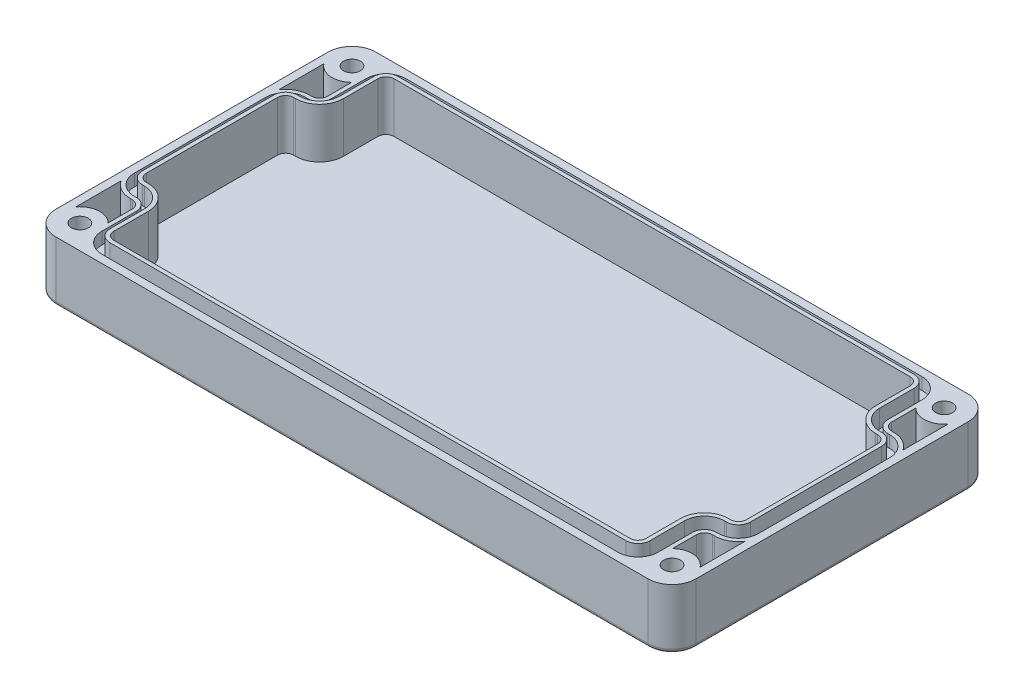
SolidWorks part; units mm, degrees
ref_plane "Спереди" through (0, 0, 0) normal (0, 0, 1) x (1, 0, 0)
ref_plane "Сверху" through (0, 0, 0) normal (0, 1, 0) x (1, 0, 0)
ref_plane "Справа" through (0, 0, 0) normal (1, 0, 0) x (0, 0, -1)
sketch "Эскиз1" plane through (0, 0, 0) normal (0, 1, 0) x (1, 0, 0)
  line L1 (-74, 40) -> (74, 40)
  line L2 (-80, 34) -> (-80, -34)
  line L3 (-74, -40) -> (74, -40)
  line L4 (80, 34) -> (80, -34)
  line L5 (-80, 40) -> (80, -40) construction
  line L6 (-80, -40) -> (80, 40) construction
  arc A0 (74, 40) -> (80, 34) centre (74, 34) cw
  arc A1 (80, -34) -> (74, -40) centre (74, -34) cw
  arc A2 (-74, -40) -> (-80, -34) centre (-74, -34) cw
  arc A3 (-80, 34) -> (-74, 40) centre (-74, 34) cw
  point P0 (0, 0)
  dimension "D3" = 6
  dimension "D1" = 160
  dimension "D2" = 80
extrude "Бобышка-Вытянуть1" add sketch "Эскиз1" along normal blind 15
sketch "Эскиз2" plane through (0, 0, 0) normal (0, 1, 0) x (1, 0, 0)
  line L0 (-66.5, 33) -> (-66.5, 24.4)
  line L1 (-72.5, 18.4) -> (-73, 18.4)
  line L2 (-75, 16.4) -> (-75, -16.4)
  line L3 (-73, -18.4) -> (-72.5, -18.4)
  line L4 (-66.5, -24.4) -> (-66.5, -33)
  line L5 (-64.5, -35) -> (64.5, -35)
  line L6 (66.5, -33) -> (66.5, -24.4)
  line L7 (72.5, -18.4) -> (73, -18.4)
  line L8 (75, -16.4) -> (75, 16.4)
  line L9 (73, 18.4) -> (72.5, 18.4)
  line L10 (66.5, 24.4) -> (66.5, 33)
  line L11 (64.5, 35) -> (-64.5, 35)
  line L12 (-75, 0) -> (75, 0) construction
  line L13 (0, 35) -> (0, -35) construction
  arc A0 (66.5, 24.4) -> (72.5, 18.4) centre (72.5, 24.4) ccw
  arc A1 (72.5, -18.4) -> (66.5, -24.4) centre (72.5, -24.4) ccw
  arc A2 (-66.5, -24.4) -> (-72.5, -18.4) centre (-72.5, -24.4) ccw
  arc A3 (-72.5, 18.4) -> (-66.5, 24.4) centre (-72.5, 24.4) ccw
  arc A4 (64.5, 35) -> (66.5, 33) centre (64.5, 33) cw
  arc A5 (73, 18.4) -> (75, 16.4) centre (73, 16.4) cw
  arc A6 (75, -16.4) -> (73, -18.4) centre (73, -16.4) cw
  arc A7 (66.5, -33) -> (64.5, -35) centre (64.5, -33) cw
  arc A8 (-64.5, -35) -> (-66.5, -33) centre (-64.5, -33) cw
  arc A9 (-73, -18.4) -> (-75, -16.4) centre (-73, -16.4) cw
  arc A10 (-75, 16.4) -> (-73, 18.4) centre (-73, 16.4) cw
  arc A11 (-66.5, 33) -> (-64.5, 35) centre (-64.5, 33) cw
  dimension "D4" = 150
  dimension "D1" = 6
  dimension "D2" = 2
  dimension "D3" = 70
  dimension "D5" = 36.8
  dimension "D6" = 133
extrude "Вырез-Вытянуть1" cut sketch "Эскиз2" along normal up to surface (15 mm away) from offset 4 up to face at (0, 15, 0)
sketch "Эскиз3" plane through (0, 0, 0) normal (0, 1, 0) x (1, 0, 0)
  line L8 (-78, 34) -> (-78, -34)
  line L9 (-74, -38) -> (74, -38)
  line L10 (78, -34) -> (78, 34)
  line L11 (74, 38) -> (-74, 38)
  line L12 (-78, 34) -> (-78, -34)
  line L13 (-74, -38) -> (74, -38)
  line L14 (78, -34) -> (78, 34)
  line L15 (74, 38) -> (-74, 38)
  line L36 (70.5, 24.4) -> (70.5, 33)
  line L37 (73, 22.4) -> (72.5, 22.4)
  line L38 (79, -16.4) -> (79, 16.4)
  line L39 (72.5, -22.4) -> (73, -22.4)
  line L40 (70.5, -33) -> (70.5, -24.4)
  line L41 (-64.5, -39) -> (64.5, -39)
  line L42 (-70.5, -24.4) -> (-70.5, -33)
  line L43 (-73, -22.4) -> (-72.5, -22.4)
  line L44 (-79, 16.4) -> (-79, -16.4)
  line L45 (-72.5, 22.4) -> (-73, 22.4)
  line L46 (-70.5, 33) -> (-70.5, 24.4)
  line L47 (64.5, 39) -> (-64.5, 39)
  line L48 (70.5, 24.4) -> (70.5, 33)
  line L49 (73, 22.4) -> (72.5, 22.4)
  line L50 (79, -16.4) -> (79, 16.4)
  line L51 (72.5, -22.4) -> (73, -22.4)
  line L52 (70.5, -33) -> (70.5, -24.4)
  line L53 (-64.5, -39) -> (64.5, -39)
  line L54 (-70.5, -24.4) -> (-70.5, -33)
  line L55 (-73, -22.4) -> (-72.5, -22.4)
  line L56 (-79, 16.4) -> (-79, -16.4)
  line L57 (-72.5, 22.4) -> (-73, 22.4)
  line L58 (-70.5, 33) -> (-70.5, 24.4)
  line L59 (64.5, 39) -> (-64.5, 39)
  circle A0 centre (-74, 34) radius 5
  arc A8 (-74, 38) -> (-78, 34) centre (-74, 34) ccw
  arc A9 (-78, -34) -> (-74, -38) centre (-74, -34) ccw
  arc A10 (74, -38) -> (78, -34) centre (74, -34) ccw
  arc A11 (78, 34) -> (74, 38) centre (74, 34) ccw
  arc A12 (-74, 38) -> (-78, 34) centre (-74, 34) ccw
  arc A13 (-78, -34) -> (-74, -38) centre (-74, -34) ccw
  arc A14 (74, -38) -> (78, -34) centre (74, -34) ccw
  arc A15 (78, 34) -> (74, 38) centre (74, 34) ccw
  arc A36 (70.5, 33) -> (64.5, 39) centre (64.5, 33) ccw
  arc A37 (70.5, 24.4) -> (72.5, 22.4) centre (72.5, 24.4) ccw
  arc A38 (79, 16.4) -> (73, 22.4) centre (73, 16.4) ccw
  arc A39 (73, -22.4) -> (79, -16.4) centre (73, -16.4) ccw
  arc A40 (72.5, -22.4) -> (70.5, -24.4) centre (72.5, -24.4) ccw
  arc A41 (64.5, -39) -> (70.5, -33) centre (64.5, -33) ccw
  arc A42 (-70.5, -33) -> (-64.5, -39) centre (-64.5, -33) ccw
  arc A43 (-70.5, -24.4) -> (-72.5, -22.4) centre (-72.5, -24.4) ccw
  arc A44 (-79, -16.4) -> (-73, -22.4) centre (-73, -16.4) ccw
  arc A45 (-73, 22.4) -> (-79, 16.4) centre (-73, 16.4) ccw
  arc A46 (-72.5, 22.4) -> (-70.5, 24.4) centre (-72.5, 24.4) ccw
  arc A47 (-64.5, 39) -> (-70.5, 33) centre (-64.5, 33) ccw
  arc A48 (70.5, 33) -> (64.5, 39) centre (64.5, 33) ccw
  arc A49 (70.5, 24.4) -> (72.5, 22.4) centre (72.5, 24.4) ccw
  arc A50 (79, 16.4) -> (73, 22.4) centre (73, 16.4) ccw
  arc A51 (73, -22.4) -> (79, -16.4) centre (73, -16.4) ccw
  arc A52 (72.5, -22.4) -> (70.5, -24.4) centre (72.5, -24.4) ccw
  arc A53 (64.5, -39) -> (70.5, -33) centre (64.5, -33) ccw
  arc A54 (-70.5, -33) -> (-64.5, -39) centre (-64.5, -33) ccw
  arc A55 (-70.5, -24.4) -> (-72.5, -22.4) centre (-72.5, -24.4) ccw
  arc A56 (-79, -16.4) -> (-73, -22.4) centre (-73, -16.4) ccw
  arc A57 (-73, 22.4) -> (-79, 16.4) centre (-73, 16.4) ccw
  arc A58 (-72.5, 22.4) -> (-70.5, 24.4) centre (-72.5, 24.4) ccw
  arc A59 (-64.5, 39) -> (-70.5, 33) centre (-64.5, 33) ccw
  dimension "D3" = 10
  dimension "D1" = 2
  dimension "D2" = 4
extrude "Вырез-Вытянуть2" cut sketch "Эскиз3" along normal up to surface (15 mm away) from offset 2.5 contours L57 A58 L58 A0 L12 A57 region at (-74.5192, 0, -25.7251) up to face at (0, 15, 0)
mirror "Зеркальное отражение1" about plane through (0, 0, 0) normal (0, 0, 1) of "Вырез-Вытянуть2"
mirror "Зеркальное отражение2" about plane through (0, 0, 0) normal (1, 0, 0) of "Зеркальное отражение1"
extrude "Вытянуть-Тонкостенный1" add sketch "Эскиз2<2>" along normal blind 1.5 from surface thin contours L11 A11 L0 A3 L1 A10 L2 A9 L3 A2 L4 A8 L5 A7 L6 A1 L7 A6 L8 A5 L9 A0 L10 A4 starting at face at (-73.7587, 15, 24.81) thin type one direction wall 1
sketch "Эскиз2<2>" plane through (0, 0, 0) normal (0, 1, 0) x (1, 0, 0) same geometry as "Эскиз2"
sketch "Эскиз6" plane through (0, 0, 0) normal (0, 1, 0) x (1, 0, 0)
  circle A0 centre (-74, 34) radius 3.75
  circle A1 centre (-74, -34) radius 3.75
  circle A2 centre (74, -34) radius 3.75
  circle A3 centre (74, 34) radius 3.75
  dimension "D1" = 7.5
extrude "Вырез-Вытянуть3" cut sketch "Эскиз6" along normal blind 3
sketch "Эскиз7" plane through (0, 0, 0) normal (0, 1, 0) x (1, 0, 0)
  circle A0 centre (-74, 34) radius 2.1
  circle A1 centre (-74, -34) radius 2.1
  circle A2 centre (74, -34) radius 2.1
  circle A3 centre (74, 34) radius 2.1
  dimension "D1" = 4.2
extrude "Вырез-Вытянуть4" cut sketch "Эскиз7" along normal up to surface (15 mm away) up to face at (0, 15, 0)
sketch "Эскиз10" plane through (0, 0, 0) normal (0, 1, 0) x (1, 0, 0)
  line L24 (67.5, 24.4) -> (67.5, 33)
  line L25 (64.5, 36) -> (-64.5, 36)
  line L26 (-67.5, 33) -> (-67.5, 24.4)
  line L27 (-72.5, 19.4) -> (-73, 19.4)
  line L28 (-76, 16.4) -> (-76, -16.4)
  line L29 (-73, -19.4) -> (-72.5, -19.4)
  line L30 (-67.5, -24.4) -> (-67.5, -33)
  line L31 (-64.5, -36) -> (64.5, -36)
  line L32 (67.5, -33) -> (67.5, -24.4)
  line L33 (72.5, -19.4) -> (73, -19.4)
  line L34 (76, -16.4) -> (76, 16.4)
  line L35 (73, 19.4) -> (72.5, 19.4)
  line L36 (67.5, 24.4) -> (67.5, 33)
  line L37 (64.5, 36) -> (-64.5, 36)
  line L38 (-67.5, 33) -> (-67.5, 24.4)
  line L39 (-72.5, 19.4) -> (-73, 19.4)
  line L40 (-76, 16.4) -> (-76, -16.4)
  line L41 (-73, -19.4) -> (-72.5, -19.4)
  line L42 (-67.5, -24.4) -> (-67.5, -33)
  line L43 (-64.5, -36) -> (64.5, -36)
  line L44 (67.5, -33) -> (67.5, -24.4)
  line L45 (72.5, -19.4) -> (73, -19.4)
  line L46 (76, -16.4) -> (76, 16.4)
  line L47 (73, 19.4) -> (72.5, 19.4)
  arc A24 (67.5, 33) -> (64.5, 36) centre (64.5, 33) ccw
  arc A25 (-64.5, 36) -> (-67.5, 33) centre (-64.5, 33) ccw
  arc A26 (-72.5, 19.4) -> (-67.5, 24.4) centre (-72.5, 24.4) ccw
  arc A27 (-73, 19.4) -> (-76, 16.4) centre (-73, 16.4) ccw
  arc A28 (-76, -16.4) -> (-73, -19.4) centre (-73, -16.4) ccw
  arc A29 (-67.5, -24.4) -> (-72.5, -19.4) centre (-72.5, -24.4) ccw
  arc A30 (-67.5, -33) -> (-64.5, -36) centre (-64.5, -33) ccw
  arc A31 (64.5, -36) -> (67.5, -33) centre (64.5, -33) ccw
  arc A32 (72.5, -19.4) -> (67.5, -24.4) centre (72.5, -24.4) ccw
  arc A33 (73, -19.4) -> (76, -16.4) centre (73, -16.4) ccw
  arc A34 (76, 16.4) -> (73, 19.4) centre (73, 16.4) ccw
  arc A35 (67.5, 24.4) -> (72.5, 19.4) centre (72.5, 24.4) ccw
  arc A36 (67.5, 33) -> (64.5, 36) centre (64.5, 33) ccw
  arc A37 (-64.5, 36) -> (-67.5, 33) centre (-64.5, 33) ccw
  arc A38 (-72.5, 19.4) -> (-67.5, 24.4) centre (-72.5, 24.4) ccw
  arc A39 (-73, 19.4) -> (-76, 16.4) centre (-73, 16.4) ccw
  arc A40 (-76, -16.4) -> (-73, -19.4) centre (-73, -16.4) ccw
  arc A41 (-67.5, -24.4) -> (-72.5, -19.4) centre (-72.5, -24.4) ccw
  arc A42 (-67.5, -33) -> (-64.5, -36) centre (-64.5, -33) ccw
  arc A43 (64.5, -36) -> (67.5, -33) centre (64.5, -33) ccw
  arc A44 (72.5, -19.4) -> (67.5, -24.4) centre (72.5, -24.4) ccw
  arc A45 (73, -19.4) -> (76, -16.4) centre (73, -16.4) ccw
  arc A46 (76, 16.4) -> (73, 19.4) centre (73, 16.4) ccw
  arc A47 (67.5, 24.4) -> (72.5, 19.4) centre (72.5, 24.4) ccw
  dimension "D1" = 1
extrude "Вырез-Вытянуть-Тонкостенный2" cut sketch "Эскиз10" against normal blind 3 from surface thin starting at face at (74, 15, 31.9) thin type one direction wall 2
fillet "Скругление1" radius 1 8 edges at (78.2426, 0, -38.2426) (80, 0, 0) (78.2426, 0, 38.2426) (0, 0, 40) (-78.2426, 0, 38.2426) (-80, 0, 0) (-78.2426, 0, -38.2426) (0, 0, -40)
